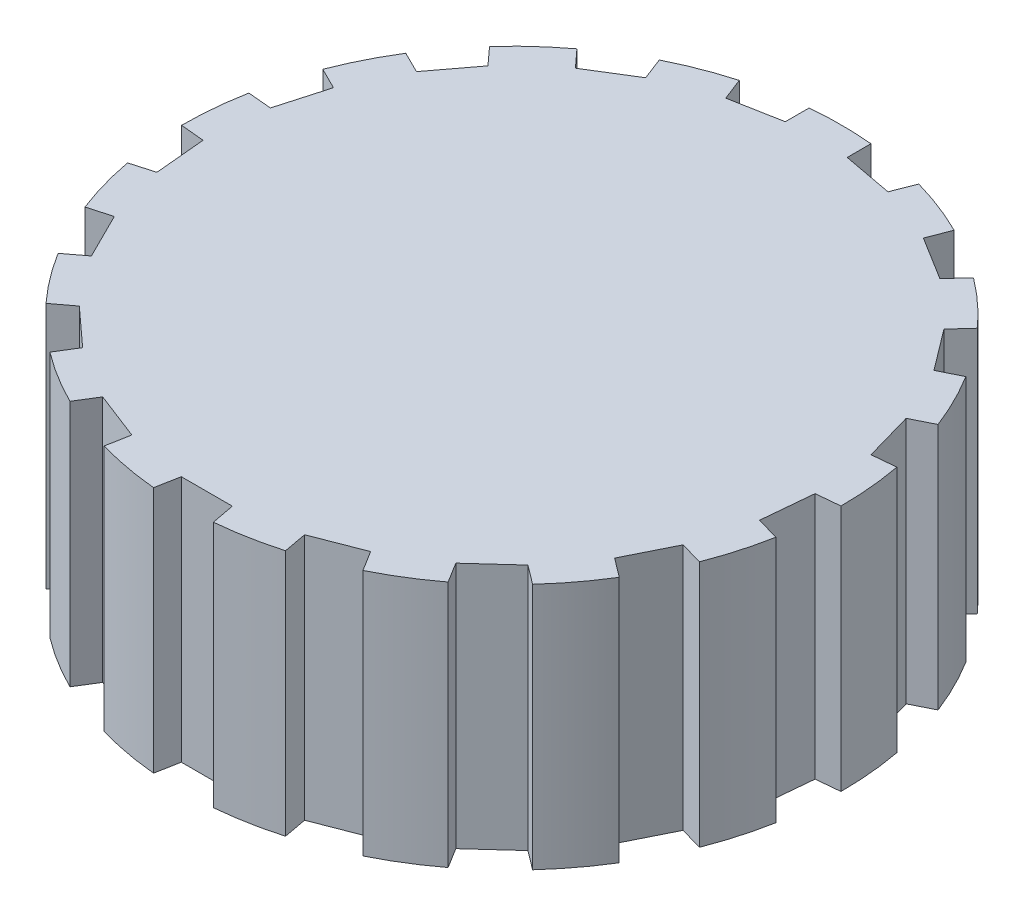
SolidWorks part; units mm, degrees
ref_plane "Front Plane" through (0, 0, 0) normal (0, 0, 1) x (1, 0, 0)
ref_plane "Top Plane" through (0, 0, 0) normal (0, 1, 0) x (1, 0, 0)
ref_plane "Right Plane" through (0, 0, 0) normal (1, 0, 0) x (0, 0, -1)
sketch "Sketch1" plane through (0, 0, 0) normal (0, 1, 0) x (1, 0, 0)
  circle A0 centre (0, 0) radius 25.4
extrude "Boss-Extrude1" add sketch "Sketch1" along normal blind 19.05
sketch "Sketch2" plane through (0, 0, 0) normal (0, -1, 0) x (1, 0, 0)
  line L4 (0, 25.4) -> (2.3241, 25.4)
  line L5 (0, 25.4) -> (-2.3241, 25.4)
  line L6 (-1.9657, 23.495) -> (1.9657, 23.495)
  line L7 (2.3241, 25.4) -> (1.9657, 23.495)
  line L8 (-2.3241, 25.4) -> (-1.9657, 23.495)
  circle A0 centre (0, 0) radius 25.4 construction
  dimension "D1" = 1.905
  dimension "D2" = 25.4
extrude "Cut-Extrude1" cut sketch "Sketch2" against normal blind 33
pattern_circular "CirPattern1" count 17 over 360 about axis through (0, 0, 0) along (0, 1, 0) of "Cut-Extrude1"
